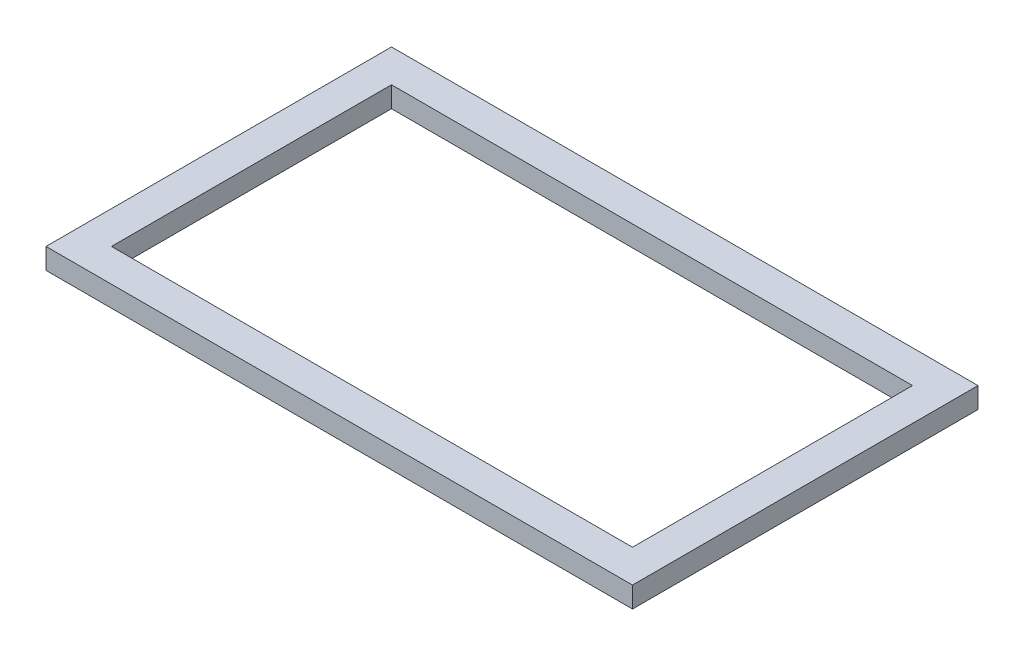
SolidWorks part; units mm, degrees
ref_plane "Front Plane" through (0, 0, 0) normal (0, 0, 1) x (1, 0, 0)
ref_plane "Top Plane" through (0, 0, 0) normal (0, 1, 0) x (1, 0, 0)
ref_plane "Right Plane" through (0, 0, 0) normal (1, 0, 0) x (0, 0, -1)
sketch "Sketch1" plane through (0, 0, 0) normal (0, 1, 0) x (1, 0, 0)
  line L1 (-179.135, 105.525) -> (179.135, 105.525)
  line L2 (-179.135, 105.525) -> (-179.135, -105.525)
  line L3 (-179.135, -105.525) -> (179.135, -105.525)
  line L4 (179.135, 105.525) -> (179.135, -105.525)
  line L5 (-179.135, 105.525) -> (179.135, -105.525) construction
  line L6 (-179.135, -105.525) -> (179.135, 105.525) construction
  point P0 (0, 0)
  dimension "D1" = 358.27
  dimension "D2" = 211.05
extrude "Boss-Extrude1" add sketch "Sketch1" along normal blind 12.7
sketch "Sketch2" plane through (0, 12.7, 0) normal (0, 1, 0) x (1, 0, 0)
  line L0 (179.135, 105.525) -> (-179.135, 105.525) construction
  line L1 (-159.135, 85.525) -> (159.135, 85.525)
  line L2 (-159.135, 85.525) -> (-159.135, -85.525)
  line L3 (-159.135, -85.525) -> (159.135, -85.525)
  line L4 (159.135, 85.525) -> (159.135, -85.525)
  line L5 (-159.135, 85.525) -> (159.135, -85.525) construction
  line L6 (-159.135, -85.525) -> (159.135, 85.525) construction
  line L7 (-179.135, 105.525) -> (-179.135, -105.525) construction
  point P0 (0, 0)
  dimension "D1" = 20
  dimension "D2" = 20
extrude "Cut-Extrude1" cut sketch "Sketch2" against normal blind 12.7
